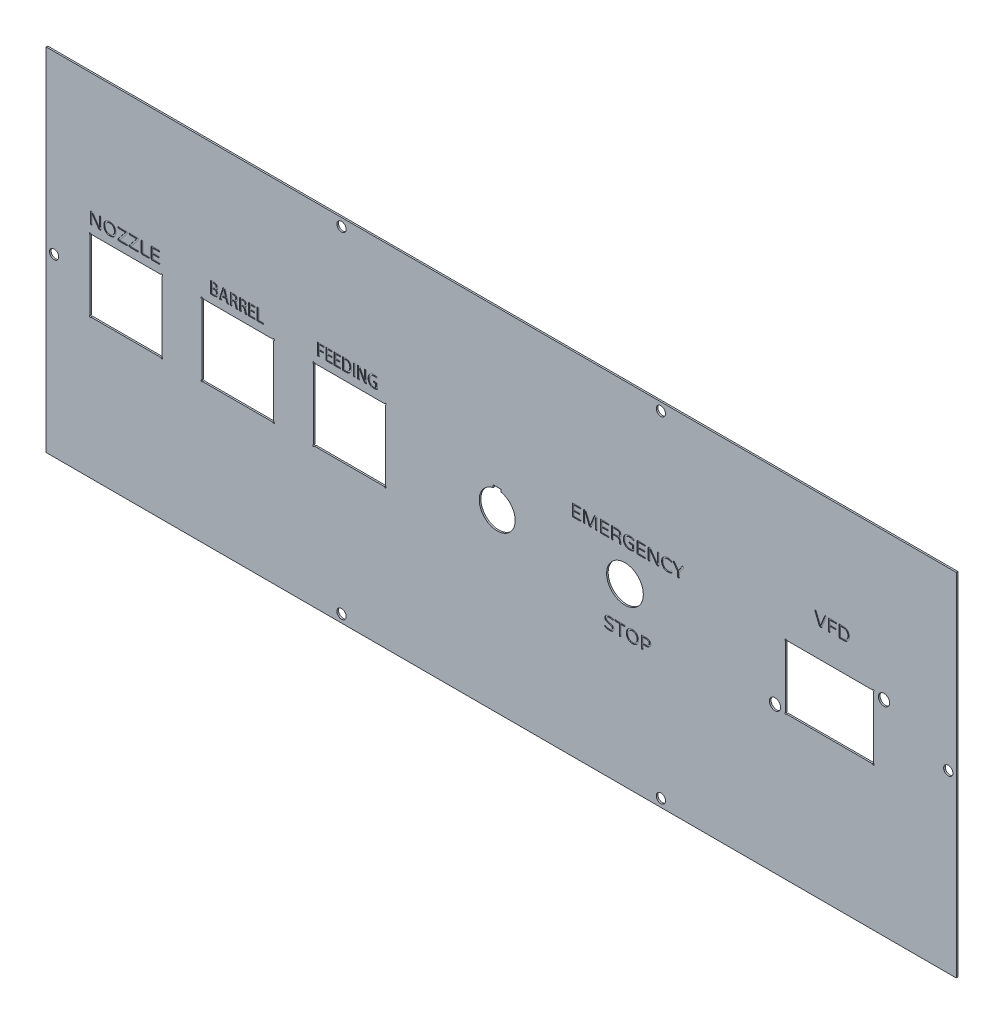
SolidWorks part; units mm, degrees
material "ASTM A36 Acier"
ref_plane "Front Plane" through (0, 0, 0) normal (0, 0, 1) x (1, 0, 0)
ref_plane "Top Plane" through (0, 0, 0) normal (0, 1, 0) x (1, 0, 0)
ref_plane "Right Plane" through (0, 0, 0) normal (1, 0, 0) x (0, 0, -1)
sketch "Sketch1" plane through (0, 0, 0) normal (0, 0, 1) x (1, 0, 0)
  line L1 (285, -110) -> (-285, -110)
  line L2 (285, -110) -> (285, 110)
  line L3 (285, 110) -> (-285, 110)
  line L4 (-285, -110) -> (-285, 110)
  line L5 (285, -110) -> (-285, 110) construction
  line L6 (285, 110) -> (-285, -110) construction
  point P0 (0, 0)
  dimension "D1" = 570
  dimension "D2" = 220
base flange "Base-Flange1" sketch "Sketch1" thickness 1 reverse thickness direction no parameters "D1"=1
sketch "Sketch33" plane through (0, 0, 0) normal (0, 0, 1) x (1, 0, 0)
  line L0 (0, 0) -> (50000, 0) construction
  line L1 (-165, 85) -> (-165, 0) construction
  line L2 (-257.5, -22.5) -> (-212.5, -22.5)
  line L3 (-257.5, -22.5) -> (-257.5, 22.5)
  line L4 (-257.5, 22.5) -> (-212.5, 22.5)
  line L5 (-212.5, -22.5) -> (-212.5, 22.5)
  line L6 (-257.5, -22.5) -> (-212.5, 22.5) construction
  line L7 (-257.5, 22.5) -> (-212.5, -22.5) construction
  line L8 (-187.5, 22.5) -> (-142.5, 22.5)
  line L9 (0, 10.9687) -> (0, 12.5)
  line L18 (-285, 110) -> (-285, -110) construction
  line L25 (-142.5, -22.5) -> (-142.5, 22.5)
  line L30 (0, 12.5) -> (-5, 12.5)
  line L31 (178.1223, -20) -> (233.1223, -20)
  line L32 (-187.5, -22.5) -> (-142.5, -22.5)
  line L33 (-187.5, -22.5) -> (-187.5, 22.5)
  line L34 (-117.5, 22.5) -> (-72.5, 22.5)
  line L35 (-72.5, -22.5) -> (-72.5, 22.5)
  line L36 (-117.5, -22.5) -> (-72.5, -22.5)
  line L37 (-117.5, -22.5) -> (-117.5, 22.5)
  line L39 (-72.5, 22.5) -> (-117.5, -22.5) construction
  line L40 (-117.5, 22.5) -> (-95, 0) construction
  line L41 (-187.5, 22.5) -> (-142.5, -22.5) construction
  line L42 (-142.5, 22.5) -> (-165, 0) construction
  line L43 (-235, 0) -> (-95, 0) construction
  line L44 (-5, 12.5) -> (-5, 10.9687)
  line L45 (178.1223, -20) -> (178.1223, 20)
  line L46 (178.1223, 20) -> (233.1223, 20)
  line L47 (233.1223, -20) -> (233.1223, 20)
  line L48 (178.1223, -20) -> (233.1223, 20) construction
  line L49 (178.1223, 20) -> (233.1223, -20) construction
  line L50 (-2.5, 12.5) -> (-2.5, 0) construction
  line L51 (285, -110) -> (285, 110) construction
  circle A0 centre (77.5, 0) radius 11.5
  arc A1 (-5, 10.9687) -> (0, 10.9687) centre (-2.5, 0) ccw
  circle A2 centre (171.5, -18.277) radius 3.5
  circle A3 centre (239.7445, 18.27) radius 3.5
  point P3 (-235, 0)
  point P8 (205.6223, 0)
  dimension "D6" = 23
  dimension "D16" = 22.5
  dimension "D13" = 27.5
  dimension "D21" = 7
  dimension "D22" = 36.547
  dimension "D23" = 68.2445
  dimension "D24" = 7
  dimension "D25" = 18.277
  dimension "D26" = 45.2555
  dimension "D2" = 45
  dimension "D3" = 45
  dimension "D5" = 45
  dimension "D10" = 45
  dimension "D11" = 70
  dimension "D12" = 80
  dimension "D14" = 70
  dimension "D17" = 55
  dimension "D18" = 40
  dimension "D19" = 34.1223
  dimension "D4" = 45
  dimension "D20" = 12.5
extrude "Cut-Extrude1" cut sketch "Sketch33" against normal through all and the other way through all normal cut yes
edge flange "Edge-Flange1" [suppressed] sketch "Sketch14" flange profiles "Sketch14", "Sketch15", "Sketch16", "Sketch17" flange angle 90 flange position material inside bend radius 1 thickness 1
sketch "Sketch14" plane through (0, 100, -1) normal (0, 1, 0) x (1, 0, 0)
  line L0 (275, 0) -> (-275, 0) construction
  line L1 (275, 0) -> (-275, 0)
  line L2 (-275, 0) -> (-275, 199)
  line L3 (-275, 199) -> (275, 199)
  line L4 (275, 199) -> (275, 0)
sketch "Sketch15" plane through (-275, 0, -1) normal (-1, 0, 0) x (0, 1, 0)
  line L0 (100, 0) -> (-100, 0) construction
  line L1 (100, 0) -> (-100, 0)
  line L2 (-100, 0) -> (-100, 199)
  line L3 (-100, 199) -> (100, 199)
  line L4 (100, 199) -> (100, 0)
sketch "Sketch16" plane through (0, -100, -1) normal (0, -1, 0) x (-1, 0, 0)
  line L0 (275, 0) -> (-275, 0) construction
  line L1 (275, 0) -> (-275, 0)
  line L2 (-275, 0) -> (-275, 199)
  line L3 (-275, 199) -> (275, 199)
  line L4 (275, 199) -> (275, 0)
sketch "Sketch17" plane through (275, 0, -1) normal (1, 0, 0) x (0, -1, 0)
  line L0 (100, 0) -> (-100, 0) construction
  line L1 (100, 0) -> (-100, 0)
  line L2 (-100, 0) -> (-100, 199)
  line L3 (-100, 199) -> (100, 199)
  line L4 (100, 199) -> (100, 0)
bend "EdgeBend1" bend radius 1 bend angle 90 parameters "D5"=1
bend "EdgeBend2" bend radius 1 bend angle 90 parameters "D5"=2
bend "EdgeBend3" bend radius 1 bend angle 90 parameters "D5"=3
bend "EdgeBend4" bend radius 1 bend angle 90 parameters "D5"=4, "D6"=10, "D7"=200
ref_plane "Plane1" [suppressed] through (274, -98.2929, -200) normal (0, 1, 0) x (1, 0, 0)
ref_plane "Plane2" [suppressed] through (273.2929, 99, -200) normal (-1, 0, 0) x (0, 0, 1)
ref_plane "Plane3" [suppressed] through (274, 98.2929, -200) normal (0, 1, 0) x (1, 0, 0)
edge flange "Edge-Flange2" [suppressed] sketch "Sketch29" flange profiles "Sketch29", "Sketch30", "Sketch31", "Sketch32" flange angle 90 flange position material inside bend radius 1 thickness 1
sketch "Sketch29" plane through (0, 99, -200) normal (0, 0, -1) x (1, 0, 0)
  line L0 (273.2929, 0) -> (-273.2929, 0) construction
  line L1 (273.2929, 0) -> (-273.2929, 0)
  line L2 (-273.2929, 0) -> (-273.2929, 9)
  line L3 (-273.2929, 9) -> (273.2929, 9)
  line L4 (273.2929, 9) -> (273.2929, 0)
sketch "Sketch30" plane through (274, 0, -200) normal (0, 0, -1) x (0, -1, 0)
  line L0 (98.2929, 0) -> (-98.2929, 0) construction
  line L1 (98.2929, 0) -> (-98.2929, 0)
  line L2 (-98.2929, 0) -> (-98.2929, 9)
  line L3 (-98.2929, 9) -> (98.2929, 9)
  line L4 (98.2929, 9) -> (98.2929, 0)
sketch "Sketch31" plane through (0, -99, -200) normal (0, 0, -1) x (-1, 0, 0)
  line L0 (273.2929, 0) -> (-273.2929, 0) construction
  line L1 (273.2929, 0) -> (-273.2929, 0)
  line L2 (-273.2929, 0) -> (-273.2929, 9)
  line L3 (-273.2929, 9) -> (273.2929, 9)
  line L4 (273.2929, 9) -> (273.2929, 0)
sketch "Sketch32" plane through (-274, 0, -200) normal (0, 0, -1) x (0, 1, 0)
  line L0 (98.2929, 0) -> (-98.2929, 0) construction
  line L1 (98.2929, 0) -> (-98.2929, 0)
  line L2 (-98.2929, 0) -> (-98.2929, 9)
  line L3 (-98.2929, 9) -> (98.2929, 9)
  line L4 (98.2929, 9) -> (98.2929, 0)
bend "EdgeBend5" bend radius 1 bend angle 90 parameters "D5"=5
bend "EdgeBend6" bend radius 1 bend angle 90 parameters "D5"=6
bend "EdgeBend7" bend radius 1 bend angle 90 parameters "D5"=7
bend "EdgeBend8" bend radius 1 bend angle 90 parameters "D5"=8, "D6"=10, "D7"=10
sketch "Sketch34" [suppressed] plane through (0, 100, 0) normal (0, 1, 0) x (1, 0, 0)
  line L0 (273.2929, 350.3111) -> (273.2929, 49.6889) construction
  line L2 (273, 0) -> (-273, 0) construction
  circle A0 centre (263.2929, 10) radius 3.5682
  dimension "D1" = 10
  dimension "D2" = 10
extrude "Cut-Extrude2" [suppressed] cut sketch "Sketch34" against normal blind 10
pattern_linear "LPattern1" [suppressed] count 34 spacing 10
hole_wizard "Dégagement M51" positions "Esquisse1" profile "Esquisse2" hole size "M5" standard "ISO" end condition through all
sketch "Esquisse1" plane through (0, 0, 0) normal (0, 0, 1) x (1, 0, 0)
  line L1 (-100, 105) -> (100, 105) construction
  line L2 (-100, 105) -> (-100, -105) construction
  line L3 (-100, -105) -> (100, -105) construction
  line L4 (100, 105) -> (100, -105) construction
  line L5 (0, 105) -> (0, 0) construction
  line L6 (-280, 0) -> (0, 0) construction
  line L7 (0, 0) -> (280.004, 0) construction
  line L8 (285, 110) -> (-285, 110) construction
  point P0 (-100, 105)
  point P6 (280.004, 0)
  point P9 (100, -105)
  point P12 (-100, -105)
  point P15 (-280, 0)
  point P86 (100, 105)
  dimension "D1" = 210
  dimension "D2" = 200
  dimension "D3" = 280
  dimension "D4" = 280.004
  dimension "D5" = 5
sketch "Esquisse2" plane through (-100, 105, 0) normal (1, 0, 0) x (0, -1, 0)
  line L0 (0, 0) -> (0, 1)
  line L1 (0, 1) -> (2.9, 1)
  line L2 (2.9, 1) -> (2.9, 0)
  line L5 (2.9, 0) -> (0, 0)
  line L11 (0, -6.35) -> (0, 107.95) construction
  dimension "Diamètre du perçage jusqu'au prochain" = 5.8
  dimension "Profondeur du perçage jusqu'au prochain" = 1
sketch "Esquisse3" plane through (0, 0, 0) normal (0, 0, 1) x (1, 0, 0)
  line L0 (-285, 27.5) -> (-261.0966, 27.5) construction
  line L1 (-93.7206, -30) -> (49906.2794, -30) construction
  line L2 (-212.5, 22.5) -> (-257.5, 22.5) construction
  line L4 (43.4529, 20) -> (15.0317, 20) construction
  line L6 (0, 0) -> (-51.7835, 0) construction
  line L7 (0, 0) -> (0, 16.0524) construction
  text T0 "NOZZLE" font "@Adobe Heiti Std R" height in points 24
  text T1 "BARREL" font "@Adobe Heiti Std R" height in points 24
  text T2 "FEEDING" font "@Adobe Heiti Std R" height in points 24
  text T6 "EMERGENCY\r\n" font "@Adobe Heiti Std R" height in points 24
  text T7 "VFD" font "@Adobe Heiti Std R" height in points 24
  text T8 "STOP" font "@Adobe Heiti Std R" height in points 24
  dimension "D1" = 5
  dimension "D3" = 30
  dimension "D4" = 20
extrude "Enlèv. mat.-Extru.1" cut sketch "Esquisse3" against normal blind 0.5 normal cut yes
sketch "Esquisse4" plane through (0, 0, 0) normal (0, 0, 1) x (1, 0, 0)
  line L0 (-212.5, -22.5) -> (-212.5, 22.5) construction
  line L1 (-257, 22.5) -> (-213, 22.5)
  line L2 (-257.5, 22) -> (-257.5, -22)
  line L3 (-257, -22.5) -> (-213, -22.5)
  line L4 (-212.5, 22) -> (-212.5, -22)
  line L5 (-187, 22.5) -> (-143, 22.5)
  line L6 (-187.5, 22) -> (-187.5, -22)
  line L7 (-187, -22.5) -> (-143, -22.5)
  line L8 (-142.5, 22) -> (-142.5, -22)
  line L9 (-117, 22.5) -> (-73, 22.5)
  line L10 (-117.5, 22) -> (-117.5, -22)
  line L11 (-117, -22.5) -> (-73, -22.5)
  line L12 (-72.5, 22) -> (-72.5, -22)
  line L17 (178.6223, 20) -> (232.6223, 20)
  line L18 (178.1223, 19.5) -> (178.1223, -19.5)
  line L19 (178.6223, -20) -> (232.6223, -20)
  line L20 (233.1223, 19.5) -> (233.1223, -19.5)
  line L21 (-257.5, -22.5) -> (-212.5, -22.5) construction
  line L22 (-212.5, 22.5) -> (-257.5, 22.5) construction
  line L23 (-257.5, 22.5) -> (-257.5, -22.5) construction
  line L24 (-142.5, -22.5) -> (-142.5, 22.5) construction
  line L25 (-187.5, -22.5) -> (-142.5, -22.5) construction
  line L26 (-187.5, 22.5) -> (-187.5, -22.5) construction
  line L27 (-142.5, 22.5) -> (-187.5, 22.5) construction
  line L28 (-117.5, -22.5) -> (-72.5, -22.5) construction
  line L29 (-117.5, 22.5) -> (-117.5, -22.5) construction
  line L30 (-72.5, 22.5) -> (-117.5, 22.5) construction
  line L31 (-72.5, -22.5) -> (-72.5, 22.5) construction
  line L32 (233.1223, 20) -> (178.1223, 20) construction
  line L33 (178.1223, 20) -> (178.1223, -20) construction
  line L36 (178.1223, -20) -> (233.1223, -20) construction
  line L37 (233.1223, -20) -> (233.1223, 20) construction
  arc A0 (-257, 22.5) -> (-257.5, 22) centre (-257.5, 22.5) ccw
  arc A1 (-212.5, 22) -> (-213, 22.5) centre (-212.5, 22.5) ccw
  arc A2 (-213, -22.5) -> (-212.5, -22) centre (-212.5, -22.5) ccw
  arc A3 (-257.5, -22) -> (-257, -22.5) centre (-257.5, -22.5) ccw
  arc A8 (-187, 22.5) -> (-187.5, 22) centre (-187.5, 22.5) ccw
  arc A9 (-142.5, 22) -> (-143, 22.5) centre (-142.5, 22.5) ccw
  arc A10 (-143, -22.5) -> (-142.5, -22) centre (-142.5, -22.5) ccw
  arc A11 (-187.5, -22) -> (-187, -22.5) centre (-187.5, -22.5) ccw
  arc A12 (-117.5, -22) -> (-117, -22.5) centre (-117.5, -22.5) ccw
  arc A13 (-117, 22.5) -> (-117.5, 22) centre (-117.5, 22.5) ccw
  arc A14 (-72.5, 22) -> (-73, 22.5) centre (-72.5, 22.5) ccw
  arc A15 (-73, -22.5) -> (-72.5, -22) centre (-72.5, -22.5) ccw
  arc A16 (178.1223, -19.5) -> (178.6223, -20) centre (178.1223, -20) ccw
  arc A17 (178.6223, 20) -> (178.1223, 19.5) centre (178.1223, 20) ccw
  arc A18 (233.1223, 19.5) -> (232.6223, 20) centre (233.1223, 20) ccw
  arc A19 (232.6223, -20) -> (233.1223, -19.5) centre (233.1223, -20) ccw
  dimension "D1" = 1
extrude "Enlèv. mat.-Extru.3" cut sketch "Esquisse4" against normal through all contours L2 A3 L3 A2 L4 A1 L1 A0 | L11 A15 L12 A14 L9 A13 L10 A12 | L19 A19 L20 A18 L17 A17 L18 A16 | L8 A10 L7 A11 L6 A8 L5 A9 normal cut yes
sketch "Esquisse5" plane through (0, 0, -1) normal (0, 0, -1) x (-1, 0, 0)
  line L9 (-285, 110) -> (285, 110) construction
  line L10 (275, -100) -> (-275, -100)
  line L11 (275, -100) -> (275, 100)
  line L12 (275, 100) -> (-275, 100)
  line L13 (-275, -100) -> (-275, 100)
  line L14 (275, -100) -> (-275, 100) construction
  line L15 (275, 100) -> (-275, -100) construction
  line L16 (-285, -110) -> (-285, 110) construction
  line L18 (273, -98) -> (-273, -98)
  line L19 (273, -98) -> (273, 98)
  line L20 (273, 98) -> (-273, 98)
  line L21 (-273, -98) -> (-273, 98)
  line L22 (273, -98) -> (-273, 98) construction
  line L23 (273, 98) -> (-273, -98) construction
  point P0 (0, 0)
  point P9 (0, 0)
  dimension "D1" = 10
  dimension "D2" = 10
  dimension "D3" = 2
  dimension "D4" = 2
extrude "Enlèv. mat.-Extru.4" [suppressed] cut sketch "Esquisse5" against normal blind 0.25
sketch "Bend-Lines1" [suppressed] plane through (0, 0, 0) normal (0, 1, 0) x (1, 0, 0)
sketch "Bounding-Box1" [suppressed] plane through (0, 0, 0) normal (0, 1, 0) x (1, 0, 0)
sheet metal parameters "Sheet-Metal1" thickness 1 parameters "D1"=1
flat pattern "Flat-Pattern1" [suppressed]
sketch "Bend-Lines2" plane through (0, 0, 0) normal (0, 1, 0) x (1, 0, 0)
sketch3d "Bounding-Box2" [suppressed]
  line L0 (-275, -100, 0) -> (275, -100, 0) construction
  line L1 (-275, 100, 0) -> (275, 100, 0) construction
  line L2 (-275, -100, 0) -> (-275, 100, 0) construction
  line L3 (275, -100, 0) -> (275, 100, 0) construction
sheet metal parameters "Sheet-Metal2" thickness 1 parameters "D1"=1
flat pattern "Flat-Pattern1"
sketch "Bend-Lines2" plane through (0, 0, 0) normal (0, 0, 1) x (1, 0, 0)
  line L0 (274.1781, -98.2929) -> (274.1781, 98.2929) construction
  line L1 (-273.2929, -99.1781) -> (273.2929, -99.1781) construction
  line L2 (-274.1781, 98.2929) -> (-274.1781, -98.2929) construction
  line L3 (273.2929, 99.1781) -> (-273.2929, 99.1781) construction
  line L4 (274.1781, -98.2929) -> (274.1781, 98.2929) construction
  line L5 (-273.2929, -99.1781) -> (273.2929, -99.1781) construction
  line L6 (-274.1781, 98.2929) -> (-274.1781, -98.2929) construction
  line L7 (273.2929, 99.1781) -> (-273.2929, 99.1781) construction
sketch3d "Bounding-Box2" [suppressed]
  line L0 (-473.3562, -298.3562, 0) -> (473.3562, -298.3562, 0) construction
  line L1 (-473.3562, 298.3562, 0) -> (473.3562, 298.3562, 0) construction
  line L2 (-473.3562, -298.3562, 0) -> (-473.3562, 298.3562, 0) construction
  line L3 (473.3562, -298.3562, 0) -> (473.3562, 298.3562, 0) construction
bend of the flat pattern "Flatten-<EdgeBend1>1"
bend of the flat pattern "Flatten-<EdgeBend2>1"
bend of the flat pattern "Flatten-<EdgeBend3>1"
bend of the flat pattern "Flatten-<EdgeBend4>1"
sheet metal parameters "Sheet-Metal3" thickness 1 parameters "D1"=1
flat pattern "Flat-Pattern1"
sketch "Bend-Lines2" plane through (0, 0, 0) normal (0, 0, 1) x (1, 0, 0)
  line L0 (174.1781, -148.2929) -> (174.1781, 148.2929) construction
  line L1 (-173.2929, -149.1781) -> (173.2929, -149.1781) construction
  line L2 (-174.1781, 148.2929) -> (-174.1781, -148.2929) construction
  line L3 (173.2929, 149.1781) -> (-173.2929, 149.1781) construction
  line L4 (174.1781, -148.2929) -> (174.1781, 148.2929) construction
  line L5 (-173.2929, -149.1781) -> (173.2929, -149.1781) construction
  line L6 (-174.1781, 148.2929) -> (-174.1781, -148.2929) construction
  line L7 (173.2929, 149.1781) -> (-173.2929, 149.1781) construction
  line L8 (-322.5343, 147.7929) -> (-322.5343, -147.7929) construction
  line L9 (-172.7929, -297.5343) -> (172.7929, -297.5343) construction
  line L10 (322.5343, -147.7929) -> (322.5343, 147.7929) construction
  line L11 (172.7929, 297.5343) -> (-172.7929, 297.5343) construction
  line L12 (-322.5343, 147.7929) -> (-322.5343, -147.7929) construction
  line L13 (-172.7929, -297.5343) -> (172.7929, -297.5343) construction
  line L14 (322.5343, -147.7929) -> (322.5343, 147.7929) construction
  line L15 (172.7929, 297.5343) -> (-172.7929, 297.5343) construction
sketch3d "Bounding-Box2" [suppressed]
  line L0 (-331.7124, -306.7124, 0) -> (331.7124, -306.7124, 0) construction
  line L1 (-331.7124, 306.7124, 0) -> (331.7124, 306.7124, 0) construction
  line L2 (-331.7124, -306.7124, 0) -> (-331.7124, 306.7124, 0) construction
  line L3 (331.7124, -306.7124, 0) -> (331.7124, 306.7124, 0) construction
bend of the flat pattern "Flatten-<EdgeBend1>1"
bend of the flat pattern "Flatten-<EdgeBend2>1"
bend of the flat pattern "Flatten-<EdgeBend3>1"
bend of the flat pattern "Flatten-<EdgeBend4>1"
bend of the flat pattern "Flatten-<EdgeBend5>1"
bend of the flat pattern "Flatten-<EdgeBend6>1"
bend of the flat pattern "Flatten-<EdgeBend7>1"
bend of the flat pattern "Flatten-<EdgeBend8>1"
sheet metal parameters "Sheet-Metal4" thickness 1 parameters "D1"=1
flat pattern "Flat-Pattern1"
sketch "Bend-Lines2" plane through (0, 0, 0) normal (0, 0, 1) x (1, 0, 0)
sketch3d "Bounding-Box2" [suppressed]
  line L0 (-280, -105, 0) -> (280, -105, 0) construction
  line L1 (-280, 105, 0) -> (280, 105, 0) construction
  line L2 (-280, -105, 0) -> (-280, 105, 0) construction
  line L3 (280, -105, 0) -> (280, 105, 0) construction
sheet metal parameters "Sheet-Metal6" thickness 1 parameters "D1"=1
flat pattern "Flat-Pattern1"
sketch "Bend-Lines2" plane through (0, 0, 0) normal (0, 0, 1) x (1, 0, 0)
  line L0 (274.1781, -98.2929) -> (274.1781, 98.2929) construction
  line L1 (-273.2929, -99.1781) -> (273.2929, -99.1781) construction
  line L2 (-274.1781, 98.2929) -> (-274.1781, -98.2929) construction
  line L3 (273.2929, 99.1781) -> (-273.2929, 99.1781) construction
  line L4 (274.1781, -98.2929) -> (274.1781, 98.2929) construction
  line L5 (-273.2929, -99.1781) -> (273.2929, -99.1781) construction
  line L6 (-274.1781, 98.2929) -> (-274.1781, -98.2929) construction
  line L7 (273.2929, 99.1781) -> (-273.2929, 99.1781) construction
  line L8 (-472.5343, 97.7929) -> (-472.5343, -97.7929) construction
  line L9 (-272.7929, -297.5343) -> (272.7929, -297.5343) construction
  line L10 (472.5343, -97.7929) -> (472.5343, 97.7929) construction
  line L11 (272.7929, 297.5343) -> (-272.7929, 297.5343) construction
  line L12 (-472.5343, 97.7929) -> (-472.5343, -97.7929) construction
  line L13 (-272.7929, -297.5343) -> (272.7929, -297.5343) construction
  line L14 (472.5343, -97.7929) -> (472.5343, 97.7929) construction
  line L15 (272.7929, 297.5343) -> (-272.7929, 297.5343) construction
sketch3d "Bounding-Box2" [suppressed]
  line L0 (-481.7124, -306.7124, 0) -> (481.7124, -306.7124, 0) construction
  line L1 (-481.7124, 306.7124, 0) -> (481.7124, 306.7124, 0) construction
  line L2 (-481.7124, -306.7124, 0) -> (-481.7124, 306.7124, 0) construction
  line L3 (481.7124, -306.7124, 0) -> (481.7124, 306.7124, 0) construction
bend of the flat pattern "Flatten-<EdgeBend1>1"
bend of the flat pattern "Flatten-<EdgeBend2>1"
bend of the flat pattern "Flatten-<EdgeBend3>1"
bend of the flat pattern "Flatten-<EdgeBend4>1"
bend of the flat pattern "Flatten-<EdgeBend5>1"
bend of the flat pattern "Flatten-<EdgeBend6>1"
bend of the flat pattern "Flatten-<EdgeBend7>1"
bend of the flat pattern "Flatten-<EdgeBend8>1"
sheet metal parameters "Sheet-Metal7" thickness 1 parameters "D1"=1
flat pattern "Flat-Pattern1"
sketch "Bend-Lines2" plane through (0, 0, 0) normal (0, 0, 1) x (1, 0, 0)
  line L0 (274.1781, -98.2929) -> (274.1781, 98.2929) construction
  line L1 (-273.2929, -99.1781) -> (273.2929, -99.1781) construction
  line L2 (-274.1781, 98.2929) -> (-274.1781, -98.2929) construction
  line L3 (273.2929, 99.1781) -> (-273.2929, 99.1781) construction
  line L4 (274.1781, -98.2929) -> (274.1781, 98.2929) construction
  line L5 (-273.2929, -99.1781) -> (273.2929, -99.1781) construction
  line L6 (-274.1781, 98.2929) -> (-274.1781, -98.2929) construction
  line L7 (273.2929, 99.1781) -> (-273.2929, 99.1781) construction
  line L8 (-472.5343, 97.7929) -> (-472.5343, -97.7929) construction
  line L9 (-272.7929, -297.5343) -> (272.7929, -297.5343) construction
  line L10 (472.5343, -97.7929) -> (472.5343, 97.7929) construction
  line L11 (272.7929, 297.5343) -> (-272.7929, 297.5343) construction
  line L12 (-472.5343, 97.7929) -> (-472.5343, -97.7929) construction
  line L13 (-272.7929, -297.5343) -> (272.7929, -297.5343) construction
  line L14 (472.5343, -97.7929) -> (472.5343, 97.7929) construction
  line L15 (272.7929, 297.5343) -> (-272.7929, 297.5343) construction
sketch3d "Bounding-Box2" [suppressed]
  line L0 (-481.7124, -306.7124, 0) -> (481.7124, -306.7124, 0) construction
  line L1 (-481.7124, 306.7124, 0) -> (481.7124, 306.7124, 0) construction
  line L2 (-481.7124, -306.7124, 0) -> (-481.7124, 306.7124, 0) construction
  line L3 (481.7124, -306.7124, 0) -> (481.7124, 306.7124, 0) construction
bend of the flat pattern "Flatten-<EdgeBend1>1"
bend of the flat pattern "Flatten-<EdgeBend2>1"
bend of the flat pattern "Flatten-<EdgeBend3>1"
bend of the flat pattern "Flatten-<EdgeBend4>1"
bend of the flat pattern "Flatten-<EdgeBend5>1"
bend of the flat pattern "Flatten-<EdgeBend6>1"
bend of the flat pattern "Flatten-<EdgeBend7>1"
bend of the flat pattern "Flatten-<EdgeBend8>1"
sheet metal parameters "Tôlerie8" thickness 1 parameters "D1"=1
flat pattern "Flat-Pattern1"
sketch "Bend-Lines2" plane through (0, 0, 0) normal (0, 0, 1) x (1, 0, 0)
sketch3d "Bounding-Box2" [suppressed]
  line L0 (-285, -110, 0) -> (285, -110, 0) construction
  line L1 (-285, 110, 0) -> (285, 110, 0) construction
  line L2 (-285, -110, 0) -> (-285, 110, 0) construction
  line L3 (285, -110, 0) -> (285, 110, 0) construction
sheet metal parameters "Tôlerie9" thickness 1 parameters "D1"=1
flat pattern "Flat-Pattern1"
sketch "Bend-Lines2" plane through (0, 0, 0) normal (0, 0, 1) x (1, 0, 0)
sketch3d "Bounding-Box2" [suppressed]
  line L0 (-285, -110, 0) -> (285, -110, 0) construction
  line L1 (-285, 110, 0) -> (285, 110, 0) construction
  line L2 (-285, -110, 0) -> (-285, 110, 0) construction
  line L3 (285, -110, 0) -> (285, 110, 0) construction
sheet metal parameters "Tôlerie10" thickness 1 parameters "D1"=1
flat pattern "Flat-Pattern1"
sketch "Bend-Lines2" plane through (0, 0, 0) normal (0, 0, 1) x (1, 0, 0)
sketch3d "Bounding-Box2" [suppressed]
  line L0 (-285, -110, 0) -> (285, -110, 0) construction
  line L1 (-285, 110, 0) -> (285, 110, 0) construction
  line L2 (-285, -110, 0) -> (-285, 110, 0) construction
  line L3 (285, -110, 0) -> (285, 110, 0) construction
sheet metal parameters "Tôlerie11" thickness 1 parameters "D1"=1
flat pattern "Flat-Pattern1"
sketch "Bend-Lines2" plane through (0, 0, 0) normal (0, 0, 1) x (1, 0, 0)
sketch3d "Bounding-Box2" [suppressed]
  line L0 (-285, -110, 0) -> (285, -110, 0) construction
  line L1 (-285, 110, 0) -> (285, 110, 0) construction
  line L2 (-285, -110, 0) -> (-285, 110, 0) construction
  line L3 (285, -110, 0) -> (285, 110, 0) construction
